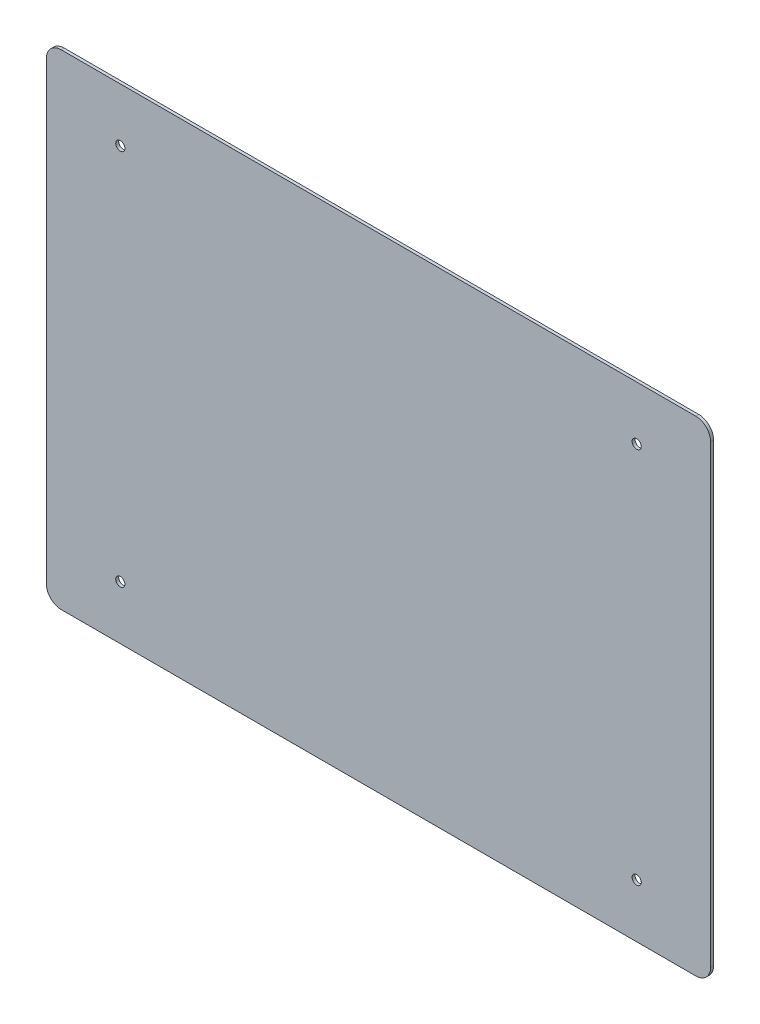
SolidWorks part; units mm, degrees
ref_plane "Front Plane" through (0, 0, 0) normal (0, 0, 1) x (1, 0, 0)
ref_plane "Top Plane" through (0, 0, 0) normal (0, 1, 0) x (1, 0, 0)
ref_plane "Right Plane" through (0, 0, 0) normal (1, 0, 0) x (0, 0, -1)
sketch "Sketch2" plane through (0, 0, 0) normal (0, 0, 1) x (1, 0, 0)
  line L1 (-225.24, 164.41) -> (225.24, 164.41)
  line L2 (-225.24, 164.41) -> (-225.24, -164.41)
  line L3 (-225.24, -164.41) -> (225.24, -164.41)
  line L4 (225.24, 164.41) -> (225.24, -164.41)
  line L5 (-225.24, 164.41) -> (225.24, -164.41) construction
  line L6 (-225.24, -164.41) -> (225.24, 164.41) construction
  point P0 (0, 0)
  dimension "Length 1" = 450.48
  dimension "Length 2" = 328.82
extrude "Boss-Extrude1" add sketch "Sketch2" along normal blind 2.032
sketch "Sketch3" plane through (0, 0, 2.032) normal (0, 0, 1) x (1, 0, 0)
  circle A0 centre (-175.117, 128.01) radius 3.1
  circle A1 centre (175.117, 128.01) radius 3.1
  circle A8 centre (-175.1171, -128.01) radius 3.1
  circle A9 centre (175.1169, -128.01) radius 3.1
  point P9 (0, 0)
  dimension "D1" = 6.2
extrude "Cut-Extrude1" cut sketch "Sketch3" against normal through all both and the other way through all
fillet "Fillet1" radius 10 4 edges at (-225.24, -164.41, 1.016) (225.24, -164.41, 1.016) (225.24, 164.41, 1.016) (-225.24, 164.41, 1.016)
sketch "Sketch4" [suppressed] plane through (0, 0, 0) normal (0, 0, -1) x (-1, 0, 0)
  circle A0 centre (-423.777, 128.01) radius 3.1
  circle A1 centre (423.777, 128.01) radius 3.1
  circle A2 centre (423.777, -128.01) radius 3.1
  circle A3 centre (-423.777, -128.01) radius 3.1
  dimension "D1" = 6.2
extrude "Cut-Extrude2" [suppressed] cut sketch "Sketch4" against normal through all both and the other way through all
fillet "Fillet2" [suppressed] radius 10
sketch "Sketch5" [suppressed] plane through (0, 0, 0) normal (0, 0, -1) x (-1, 0, 0)
  circle A0 centre (-175.117, -437.5) radius 3.1
  circle A1 centre (175.1169, -437.5) radius 3.1
  circle A2 centre (175.1169, 437.5) radius 3.1
  circle A3 centre (-175.117, 437.5) radius 3.1
  dimension "D1" = 6.2
extrude "Cut-Extrude3" [suppressed] cut sketch "Sketch5" against normal through all both and the other way through all
fillet "Fillet3" [suppressed] radius 10
